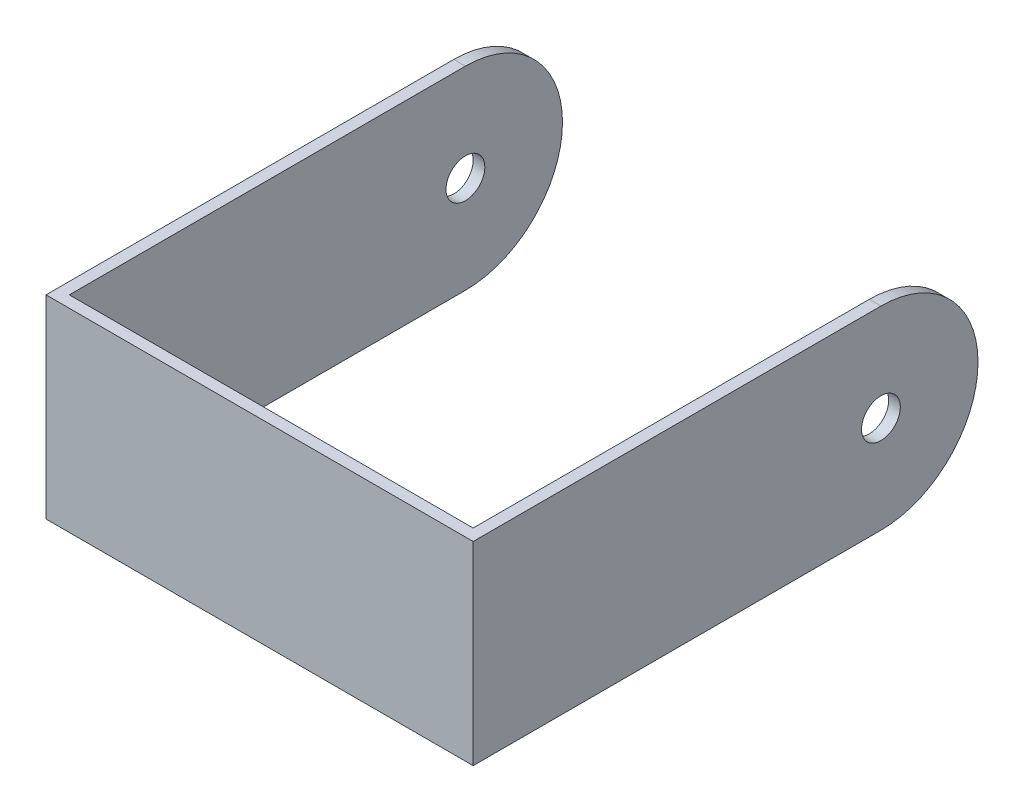
SolidWorks part; units mm, degrees
ref_plane "Front Plane" through (0, 0, 0) normal (0, 0, 1) x (1, 0, 0)
ref_plane "Top Plane" through (0, 0, 0) normal (0, 1, 0) x (1, 0, 0)
ref_plane "Right Plane" through (0, 0, 0) normal (1, 0, 0) x (0, 0, -1)
sketch "Sketch1" plane through (0, 0, 0) normal (0, 1, 0) x (1, 0, 0)
  line L0 (26, -31) -> (26, 32.5)
  line L1 (27.5, -32.5) -> (-27.5, -32.5)
  line L2 (27.5, -32.5) -> (27.5, 32.5)
  line L3 (27.5, 32.5) -> (-27.5, 32.5) construction
  line L4 (-27.5, -32.5) -> (-27.5, 32.5)
  line L5 (27.5, -32.5) -> (-27.5, 32.5) construction
  line L6 (27.5, 32.5) -> (-27.5, -32.5) construction
  line L7 (26, -31) -> (-26, -31)
  line L8 (-26, -31) -> (-26, 32.5)
  line L9 (-27.5, 32.5) -> (-26, 32.5)
  line L10 (26, 32.5) -> (27.5, 32.5)
  point P0 (0, 0)
  dimension "D1" = 65
  dimension "D2" = 55
  dimension "D3" = 1.5
extrude "Boss-Extrude1" add sketch "Sketch1" along normal mid plane 25
fillet "Fillet1" radius 12.5 4 edges at (-26.75, -12.5, -32.5) (-26.75, 12.5, -32.5) (26.75, -12.5, -32.5) (26.75, 12.5, -32.5)
sketch "Sketch2" plane through (0, 0, 0) normal (1, 0, 0) x (0, 0, -1)
  circle A0 centre (20, 0) radius 2.5
extrude "Cut-Extrude1" cut sketch "Sketch2" against normal through all both and the other way through all
mirror "Mirror1" [suppressed]
